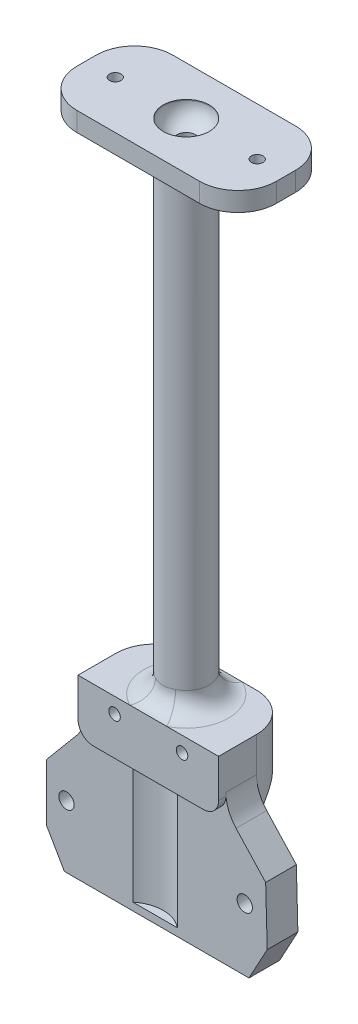
SolidWorks part; units mm, degrees
ref_plane "前视基准面" through (0, 0, 0) normal (0, 0, 1) x (1, 0, 0)
ref_plane "上视基准面" through (0, 0, 0) normal (0, 1, 0) x (1, 0, 0)
ref_plane "右视基准面" through (0, 0, 0) normal (1, 0, 0) x (0, 0, -1)
sketch "草图1" plane through (0, 0, 0) normal (0, 1, 0) x (1, 0, 0)
  line L0 (-32.0093, 0) -> (32.0093, 0) construction
  line L1 (-26, 12.5) -> (26, 12.5)
  line L2 (-26, 12.5) -> (-26, -12.5)
  line L3 (-26, -12.5) -> (26, -12.5)
  line L4 (26, 12.5) -> (26, -12.5)
  line L5 (-26, 12.5) -> (26, -12.5) construction
  line L6 (-26, -12.5) -> (26, 12.5) construction
  line L7 (0, 19.5739) -> (0, -19.5739) construction
  circle A0 centre (-18.5, 0) radius 1.5
  circle A1 centre (18.5, 0) radius 1.5
  point P0 (0, 0)
  point P9 (0, 0)
  point P12 (0, 0)
  dimension "D4" = 3
  dimension "D1" = 52
  dimension "D2" = 25
  dimension "D3" = 37
extrude "凸台-拉伸1" add sketch "草图1" along normal blind 5
sketch "草图2" plane through (0, 0, 0) normal (0, -1, 0) x (1, 0, 0)
  circle A0 centre (0, 0) radius 4
  circle A1 centre (0, 0) radius 2.5
  circle A2 centre (0, 0) radius 6
  dimension "D1" = 8
  dimension "D2" = 5
  dimension "D3" = 12
extrude "凸台-拉伸2" add sketch "草图2" along normal blind 125 contours A0 A1 region at (-3.8869, 0, 0)
fillet "圆角1" radius 10 4 edges at (26, 2.5, -12.5) (26, 2.5, 12.5) (-26, 2.5, -12.5) (-26, 2.5, 12.5)
extrude "凸台-拉伸4" add sketch "草图2<3>" along normal up to surface (125 mm away) contours A2 A0 region at (-5.8303, 0, 0) up to face at (0, -125, -2.5)
sketch "草图2<3>" plane through (0, 0, 0) normal (0, -1, 0) x (1, 0, 0) same geometry as "草图2"
fillet "圆角3" radius 5 1 edges at (0, 0, 6)
extrude "切除-拉伸1" cut sketch "草图2<4>" against normal blind 50 contours A2
sketch "草图2<4>" plane through (0, 0, 0) normal (0, -1, 0) x (1, 0, 0) same geometry as "草图2"
fillet "圆角4" radius 5 1 edges at (0, 0, -6)
sketch "草图3" plane through (0, 0, 0) normal (0, 0, 1) x (1, 0, 0)
  line L0 (0, -95.6549) -> (0, -154.3451) construction
  line L2 (18.3299, -125) -> (-18.3299, -125)
  line L3 (-18.3299, -125) -> (-18.3299, -138)
  line L4 (-18.3299, -138) -> (18.3299, -138)
  line L5 (18.3299, -138) -> (18.3299, -125)
  point P3 (0, -125)
  dimension "D1" = 13
extrude "凸台-拉伸5" add sketch "草图3" along normal blind 23 and the other way blind 10
sketch "草图4" plane through (0, -125, 0) normal (0, 1, 0) x (1, 0, 0)
  line L0 (0, 20.2764) -> (0, -20.2764) construction
  line L2 (-6.1, -20.1) -> (6.1, -20.1)
  line L3 (-6.1, -20.1) -> (-6.1, -9.9)
  line L4 (-6.1, -9.9) -> (6.1, -9.9)
  line L5 (6.1, -20.1) -> (6.1, -9.9)
  line L6 (-6.1, -20.1) -> (6.1, -9.9) construction
  line L7 (-6.1, -9.9) -> (6.1, -20.1) construction
  point P0 (0, -15)
  point P4 (0, 0)
  dimension "D1" = 10.2
  dimension "D2" = 12.2
  dimension "D3" = 15
extrude "切除-拉伸2" cut sketch "草图4" against normal blind 16
fillet "圆角5" radius 10 4 edges at (18.3299, -131.5, -10) (18.3299, -131.5, 23) (-18.3299, -131.5, -10) (-18.3299, -131.5, 23)
sketch "草图5" plane through (0, 0, 0) normal (0, 0, 1) x (1, 0, 0)
  line L4 (-18.3299, -138) -> (-28.3991, -150)
  line L5 (-28.3991, -150) -> (-28.3991, -165)
  line L6 (-28.3991, -165) -> (-23.7803, -173)
  line L7 (-23.7803, -173) -> (0.4688, -173)
  line L8 (0, -138) -> (0.6896, -189.4855) construction
  line L9 (-8.3299, -138) -> (8.3299, -138) construction
  line L10 (-18.3299, -138) -> (-8.3299, -138) construction
  line L11 (18.3299, -138) -> (28.7102, -149.2351)
  line L12 (28.7102, -149.2351) -> (29.112, -164.2297)
  line L13 (29.112, -164.2297) -> (24.357, -173)
  line L14 (24.357, -173) -> (0.4688, -173)
  line L15 (18.3299, -138) -> (-18.3299, -138)
  dimension "D1" = 130
  dimension "D2" = 150
  dimension "D3" = 12
  dimension "D4" = 15
  dimension "D5" = 8
  dimension "D6" = 150
extrude "凸台-拉伸6" add sketch "草图5" along normal blind 8
fillet "圆角7" radius 10 2 edges at (-18.3299, -138, 4) (18.3299, -138, 4)
fillet "圆角8" radius 10 1 edges at (0, -138, 0)
sketch "草图6" plane through (0, -138, 0) normal (0, -1, 0) x (1, 0, 0)
  line L0 (-6.1, 20.1) -> (-6.1, 9.9) construction
  line L1 (6.1, 20.1) -> (-6.1, 20.1) construction
  line L2 (-6.1, 9.9) -> (6.1, 9.9) construction
  line L4 (6.1, 20.1) -> (-6.1, 20.1) construction
  line L6 (-6.1, 15) -> (6.1, 15) construction
  line L11 (6.1, 20.1) -> (6.1, 9.9) construction
  line L12 (-6.1, 9.9) -> (-6.1, 20.1) construction
  line L13 (1.4979, 15.0793) -> (-0.5742, 13.6143)
  line L14 (0, 20.1) -> (0, 4.7137) construction
  arc A0 (1.4979, 15.0793) -> (-0.5742, 13.6143) centre (0, 15) ccw
  dimension "D1" = 3
sketch "草图8" plane through (0, 0, 8) normal (0, 0, 1) x (1, 0, 0)
  line L0 (0, -138) -> (0, -185.0454) construction
  line L1 (-8.3299, -138) -> (8.3299, -138) construction
  line L2 (-28.9111, -156.7324) -> (28.9111, -156.7324) construction
  line L3 (29.112, -164.2297) -> (28.7102, -149.2351) construction
  circle A0 centre (23.25, -156.7324) radius 2
  circle A1 centre (-23.25, -156.7324) radius 2
  point P8 (0, -156.7324)
  dimension "D1" = 4
  dimension "D2" = 46.5
sketch "草图9" plane through (0, -173, 0) normal (0, -1, 0) x (1, 0, 0)
  circle A1 centre (-0.1, 14.9) radius 2.5
  circle A2 centre (-0.1, 14.9) radius 9
extrude "切除-拉伸4" cut sketch "草图9" against normal blind 35
sketch "草图10" plane through (0, -173, 0) normal (0, -1, 0) x (1, 0, 0)
  line L0 (24.357, 0) -> (24.357, 8)
  line L1 (-23.7803, 0) -> (24.357, 0) construction
  line L2 (5.6784, 8) -> (24.357, 8) construction
  line L3 (24.357, 8) -> (29.112, 8) construction
  line L4 (24.357, 8) -> (-23.7803, 8)
  line L5 (-23.7803, 8) -> (-5.8784, 8) construction
  line L6 (-23.7803, 8) -> (-23.7803, 0)
  line L7 (-23.7803, 8) -> (-23.7803, 0) construction
  line L8 (-23.7803, 0) -> (24.357, 0)
extrude "凸台-拉伸9" add sketch "草图10" against normal blind 2
fillet "圆角9" radius 5 1 edges at (0, -125, -6)
extrude "切除-拉伸5" cut sketch "草图8" against normal up to next
sketch "草图11" plane through (0, -138, 0) normal (0, -1, 0) x (1, 0, 0)
  line L6 (-18.9916, 9.9) -> (18.8843, 9.9)
  line L8 (-18.9916, 9.9) -> (-18.9916, 23)
  line L9 (-18.9916, 23) -> (18.8843, 23)
  line L10 (18.8843, 9.9) -> (18.8843, 23)
  line L11 (-8.3299, 23) -> (8.3299, 23) construction
  line L15 (-6.1, 9.9) -> (6.1, 9.9) construction
  point P0 (0, 15)
extrude "切除-拉伸6" cut sketch "草图11" against normal up to next
sketch "草图12" plane through (0, -138, 0) normal (0, -1, 0) x (1, 0, 0)
  line L4 (-18.3299, 8) -> (-5.8784, 8)
  line L5 (18.3299, 9.9) -> (-18.3299, 9.9)
  line L6 (-18.3299, 9.9) -> (-18.3299, 8)
  line L9 (18.3299, 8) -> (18.3299, 9.9)
  line L10 (18.3299, 9.9) -> (-18.3299, 9.9)
  line L11 (-18.3299, 9.9) -> (-18.3299, 8)
  line L14 (18.3299, 8) -> (18.3299, 9.9)
  line L15 (-18.3299, 8) -> (-5.8784, 8)
  line L16 (5.6784, 8) -> (18.3299, 8)
  line L17 (5.6784, 8) -> (18.3299, 8)
  arc A1 (-5.8784, 8) -> (5.6784, 8) centre (-0.1, 14.9) ccw
  arc A4 (-5.8784, 8) -> (5.6784, 8) centre (-0.1, 14.9) ccw
  dimension "D1" = 0
extrude "凸台-拉伸10" add sketch "草图12" along normal blind 1
sketch "草图13" plane through (0, 0, 9.9) normal (0, 0, 1) x (1, 0, 0)
  line L0 (-8.8, -129) -> (8.8, -129) construction
  line L1 (0, -125) -> (0, -133.2638) construction
  line L2 (4.7948, -125) -> (-4.7948, -125) construction
  line L3 (0, -129) -> (0, -131.8794) construction
  line L4 (-4.7948, -125) -> (-18.3299, -125) construction
  circle A0 centre (-8.8, -129) radius 1.5
  circle A1 centre (8.8, -129) radius 1.5
  dimension "D2" = 3
  dimension "D1" = 17.6
  dimension "D3" = 4
extrude "切除-拉伸7" cut sketch "草图13" against normal up to next
sketch "草图14" plane through (0, 0, -10) normal (0, 0, -1) x (-1, 0, 0)
  line L0 (-18.3299, -134.0875) -> (-18.3299, -125) construction
  line L1 (-6.05, -130.5877) -> (-6.05, -127.4123)
  line L2 (-6.05, -127.4123) -> (-8.8, -125.8246)
  line L3 (-8.8, -125.8246) -> (-11.55, -127.4123)
  line L4 (-11.55, -127.4123) -> (-11.55, -130.5877)
  line L5 (-11.55, -130.5877) -> (-8.8, -132.1754)
  line L6 (-8.8, -132.1754) -> (-6.05, -130.5877)
  line L7 (0, -126.0772) -> (0, -128.5557) construction
  line L8 (6.05, -130.5877) -> (6.05, -127.4123)
  line L9 (8.8, -132.1754) -> (6.05, -130.5877)
  line L10 (11.55, -130.5877) -> (8.8, -132.1754)
  line L11 (11.55, -127.4123) -> (11.55, -130.5877)
  line L12 (8.8, -125.8246) -> (11.55, -127.4123)
  line L13 (6.05, -127.4123) -> (8.8, -125.8246)
  circle A0 centre (-8.8, -129) radius 2.75 construction
  dimension "D1" = 5.5
extrude "切除-拉伸8" cut sketch "草图14" against normal blind 4
fillet "圆角11" radius 4 2 edges at (18.3299, -139, 8.95) (-18.3299, -139, 8.95)
sketch "草图16" plane through (0, 0, 0) normal (0, 0, -1) x (-1, 0, 0)
  line L0 (-0.2884, -173) -> (-0.2884, -158.9113) construction
  line L1 (23.7803, -173) -> (-24.357, -173) construction
  circle A0 centre (-5.2884, -167) radius 1.25
  circle A1 centre (4.7116, -167) radius 1.25
  dimension "D2" = 2.5
  dimension "D1" = 5
  dimension "D3" = 6
extrude "切除-拉伸10" cut sketch "草图16" against normal blind 4
